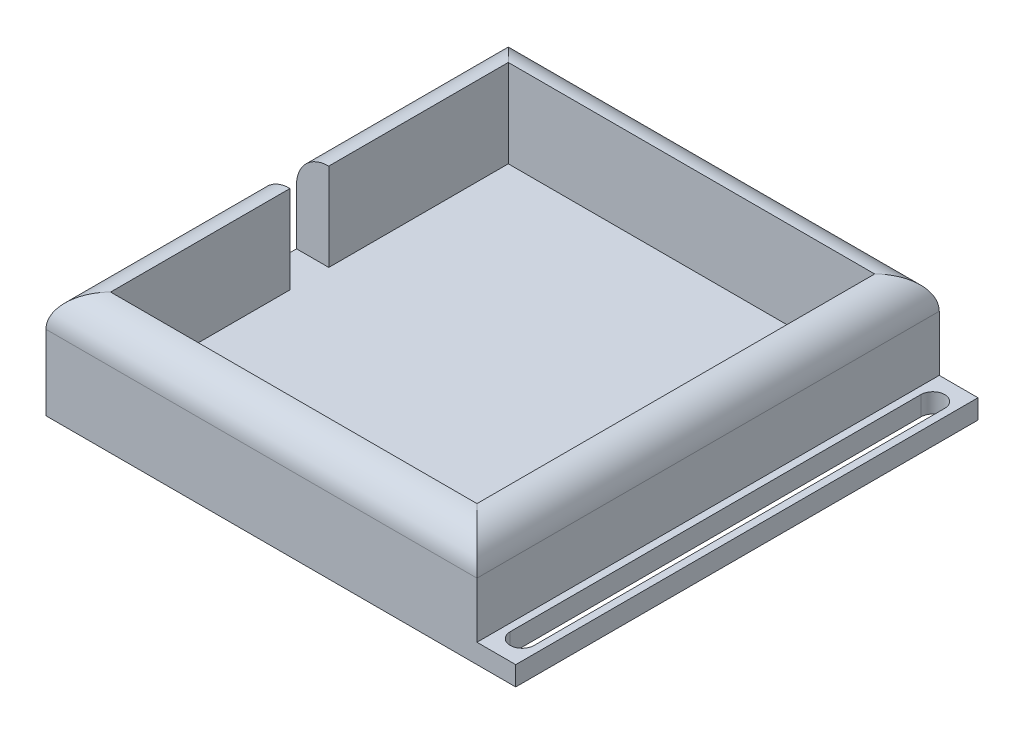
SolidWorks part; units mm, degrees
other "Markup1"
sketch "Sketch4" plane through (-5, -3, -77.8) normal (0, -1, 0) x (1, 0, 0)
ref_plane "Front Plane" through (0, 0, 0) normal (0, 0, 1) x (1, 0, 0)
ref_plane "Top Plane" through (0, 0, 0) normal (0, 1, 0) x (1, 0, 0)
ref_plane "Right Plane" through (0, 0, 0) normal (1, 0, 0) x (0, 0, -1)
sketch "Sketch1" plane through (0, 0, 0) normal (0, 1, 0) x (1, 0, 0)
  line L0 (-5, -5) -> (-5, 66.6)
  line L1 (0, 0) -> (56.75, 0)
  line L2 (0, 0) -> (0, 61.6)
  line L3 (0, 61.6) -> (56.75, 61.6)
  line L4 (56.75, 0) -> (56.75, 61.6)
  line L5 (-5, 66.6) -> (61.75, 66.6)
  line L6 (61.75, -5) -> (61.75, 66.6)
  line L7 (-5, -5) -> (61.75, -5)
  line L8 (-5, 30.8) -> (61.75, 30.8) construction
  line L9 (-5, 33.8) -> (0, 33.8)
  line L10 (-5, 27.8) -> (0, 27.8)
  dimension "D1" = 56.75
  dimension "D2" = 61.6
  dimension "D4" = 3
  dimension "D3" = 5
extrude "Boss-Extrude1" add sketch "Sketch1" along normal blind 13.6 contours L4 L8 L6 L5 L0 L9 L2 L3 | L8 L4 L1 L2 L10 L0 L7 L6 region at (-4.2426, 0, -11.4) region at (59.25, 0, -31.5574)
sketch "Sketch2" plane through (0, 0, 0) normal (0, -1, 0) x (1, 0, 0)
  line L0 (-5, -27.8) -> (-5, -33.8)
  line L12 (56.75, 0) -> (56.75, -61.6)
  line L13 (56.75, -61.6) -> (0, -61.6)
  line L14 (0, -61.6) -> (0, -33.8)
  line L15 (0, -33.8) -> (-5, -33.8)
  line L16 (-5, -33.8) -> (-5, -66.6)
  line L17 (-5, -66.6) -> (61.75, -66.6)
  line L18 (61.75, -66.6) -> (61.75, 5)
  line L19 (61.75, 5) -> (-5, 5)
  line L20 (-5, 5) -> (-5, -27.8)
  line L21 (-5, -27.8) -> (0, -27.8)
  line L22 (0, -27.8) -> (0, 0)
  line L23 (0, 0) -> (56.75, 0)
  line L24 (56.75, 0) -> (56.75, -61.6)
  line L25 (56.75, -61.6) -> (0, -61.6)
  line L26 (0, -61.6) -> (0, -33.8)
  line L27 (0, -33.8) -> (-5, -33.8)
  line L28 (-5, -33.8) -> (-5, -66.6)
  line L29 (-5, -66.6) -> (61.75, -66.6)
  line L30 (61.75, -66.6) -> (61.75, 5)
  line L31 (61.75, 5) -> (-5, 5)
  line L32 (-5, 5) -> (-5, -27.8)
  line L33 (-5, -27.8) -> (0, -27.8)
  line L34 (0, -27.8) -> (0, 0)
  line L35 (0, 0) -> (56.75, 0)
  line M13 (56.75, 0) -> (56.75, -61.6)
  line M14 (56.75, -61.6) -> (0, -61.6)
  line M15 (0, -61.6) -> (0, -33.8)
  line M16 (0, -33.8) -> (-5, -33.8)
  line M17 (-5, -33.8) -> (-5, -66.6)
  line M18 (-5, -66.6) -> (61.75, -66.6)
  line M19 (61.75, -66.6) -> (61.75, 5)
  line M20 (61.75, 5) -> (-5, 5)
  line M21 (-5, 5) -> (-5, -27.8)
  line M22 (-5, -27.8) -> (0, -27.8)
  line M23 (0, -27.8) -> (0, 0)
  line M24 (0, 0) -> (56.75, 0)
  dimension "D1" = 0
extrude "Boss-Extrude2" add sketch "Sketch2" along normal blind 3 contours M24 M13 M14 M15 M16 M17 M18 M19 M20 M21 M22 M23 | L0 M22 M16 M15 M14 M13 M24 M23 region at (28.1123, 0, -30.8) region at (-4.0211, 0, -11.4)
sketch "Sketch3" plane through (0, -3, 0) normal (0, -1, 0) x (1, 0, 0)
  line L0 (61.75, -30.8) -> (-5, -30.8) construction
  line L1 (61.75, 5) -> (-5, 5)
  line L4 (61.75, 5) -> (-5, 5)
  line L5 (-5, 5) -> (-5, -66.6)
  line L6 (-5, -66.6) -> (61.75, -66.6)
  line L7 (61.75, -66.6) -> (61.75, 5)
  line L8 (61.75, 5) -> (-5, 5)
  line L9 (-5, 5) -> (-5, -66.6)
  line L10 (-5, -66.6) -> (61.75, -66.6)
  line L11 (61.75, -66.6) -> (61.75, 5)
  line L13 (64.75, 1) -> (64.75, -62.6) construction
  line L14 (61.75, 5) -> (67.75, 5)
  line L17 (61.75, 5) -> (61.75, -66.6)
  line L18 (61.75, -66.6) -> (67.75, -66.6)
  line L19 (61.75, -66.6) -> (-5, -66.6)
  line L20 (67.75, 5) -> (67.75, -66.6)
  line L21 (66.6, 1) -> (66.6, -62.6)
  line L22 (61.75, -66.6) -> (-5, -66.6)
  line L23 (62.9, 1) -> (62.9, -62.6)
  line L26 (64.75, 5) -> (64.75, -66.6) construction
  arc A4 (66.6, 1) -> (62.9, 1) centre (64.75, 1) ccw
  arc A5 (62.9, -62.6) -> (66.6, -62.6) centre (64.75, -62.6) ccw
  point P10 (64.75, -30.8)
  point P12 (28.375, 11.05)
  point P16 (73.1979, -32.5069)
  point P19 (0, 0)
  point P20 (64.75, -61.3114)
  point P24 (28.375, -72.65)
  line M17 (61.75, -66.6) -> (61.75, 5)
  dimension "D3" = 4
  dimension "D2" = 1.85
  dimension "D4" = 6
  dimension "D5" = 4
  dimension "D1" = 0
fillet "Fillet1" radius 5 5 edges at (-5, 13.6, -50.2) (-5, 13.6, -11.4) (28.375, 13.6, -66.6) (28.375, 13.6, 5) (61.75, 13.6, -30.8)
extrude "Boss-Extrude4" add sketch "Sketch3" against normal blind 3 contours L20 L14 L18 A5 L23 A4 L21 M17 region at (64.75, -3, 4.2815)
